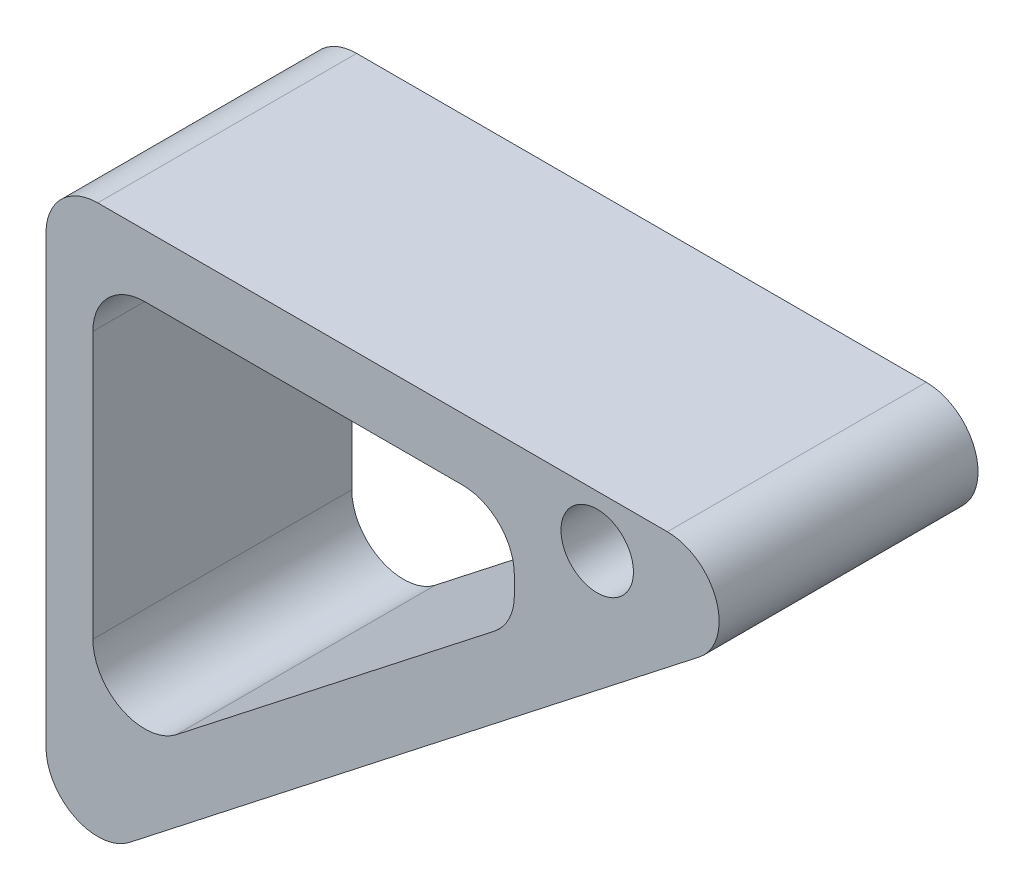
SolidWorks part; units mm, degrees
ref_plane "Front" through (0, 0, 0) normal (0, 0, 1) x (1, 0, 0)
ref_plane "Top" through (0, 0, 0) normal (0, 1, 0) x (1, 0, 0)
ref_plane "Right" through (0, 0, 0) normal (1, 0, 0) x (0, 0, -1)
sketch "Sketch2" plane through (0, 0, 0) normal (0, 0, 1) x (1, 0, 0)
  line L0 (21.0207, 22.9851) -> (-33.9793, 22.9851)
  line L1 (-38.9793, 17.9851) -> (-38.9793, -25.0149)
  line L2 (-30.8997, -28.9539) -> (24.1003, 14.0461)
  line L3 (-34.4531, 11.9981) -> (-34.4531, -13.7378)
  line L4 (-26.3735, -17.6769) -> (4.3255, 6.3241)
  line L5 (6.2459, 10.2632) -> (6.2459, 11.9981)
  line L6 (1.2459, 16.9981) -> (-29.4531, 16.9981)
  arc A0 (-38.9793, -25.0149) -> (-30.8997, -28.9539) centre (-33.9793, -25.0149) ccw
  arc A1 (-34.4531, -13.7378) -> (-26.3735, -17.6769) centre (-29.4531, -13.7378) ccw
  arc A2 (-34.4531, 11.9981) -> (-29.4531, 16.9981) centre (-29.4531, 11.9981) cw
  arc A3 (-33.9793, 22.9851) -> (-38.9793, 17.9851) centre (-33.9793, 17.9851) ccw
  arc A4 (21.0207, 22.9851) -> (24.1003, 14.0461) centre (21.0207, 17.9851) cw
  arc A5 (4.3255, 6.3241) -> (6.2459, 10.2632) centre (1.2459, 10.2632) ccw
  arc A6 (6.2459, 11.9981) -> (1.2459, 16.9981) centre (1.2459, 11.9981) ccw
  dimension "D1" = 5
  dimension "D2" = 5
  dimension "D3" = 48
  dimension "D4" = 55
extrude "Boss-Extrude1" add sketch "Sketch2" along normal blind 25 contours A4 L0 A3 L1 A0 L2 A6 L5 A5 L4 A1 L3 A2 L6 region at (24.9551, 19.3405, 0)
sketch "Sketch3" plane through (0, 0, 25) normal (0, 0, 1) x (1, 0, 0)
  line L0 (21.0207, 22.9851) -> (-33.9793, 22.9851) construction
  circle A0 centre (14.2459, 17.9851) radius 3.5
  point P2 (0, 0)
  point P5 (18.9846, 14.6549)
  point P6 (21.5467, 14.8832)
  dimension "D1" = 7
  dimension "D2" = 13
  dimension "D3" = 5
ref_plane "Plane1" through (-3.3226, 4.2498, 0) normal (0.6159, -0.7878, 0) x (-0.7878, -0.6159, 0)
sketch "Sketch4" plane through (-3.3226, 4.2498, 0) normal (0.6159, -0.7878, 0) x (-0.7878, -0.6159, 0)
  line L0 (-25.8004, -25) -> (-18.8004, -25) construction
  line L1 (-25.8004, -25) -> (-18.8004, -25)
  line L2 (-27.6377, -25) -> (-27.6377, 0) construction
  line L3 (-27.6377, -25) -> (-27.6377, 0) construction
  line L4 (-27.6377, -12.5) -> (18.9869, -12.5) construction
  line L5 (-22.3004, -25) -> (-22.3004, -12.5)
  line L6 (-22.3004, -12.5) -> (-12.6597, -12.5)
  line L7 (-12.6597, -12.5) -> (-6.8164, -12.5)
  point P8 (-22.3004, -12.5)
extrude "Cut-Extrude1" cut sketch "Sketch3" against normal through all contours A0
ref_plane "Plane2" through (0, 0, 12.5) normal (0, 0, -1) x (-1, 0, 0)
